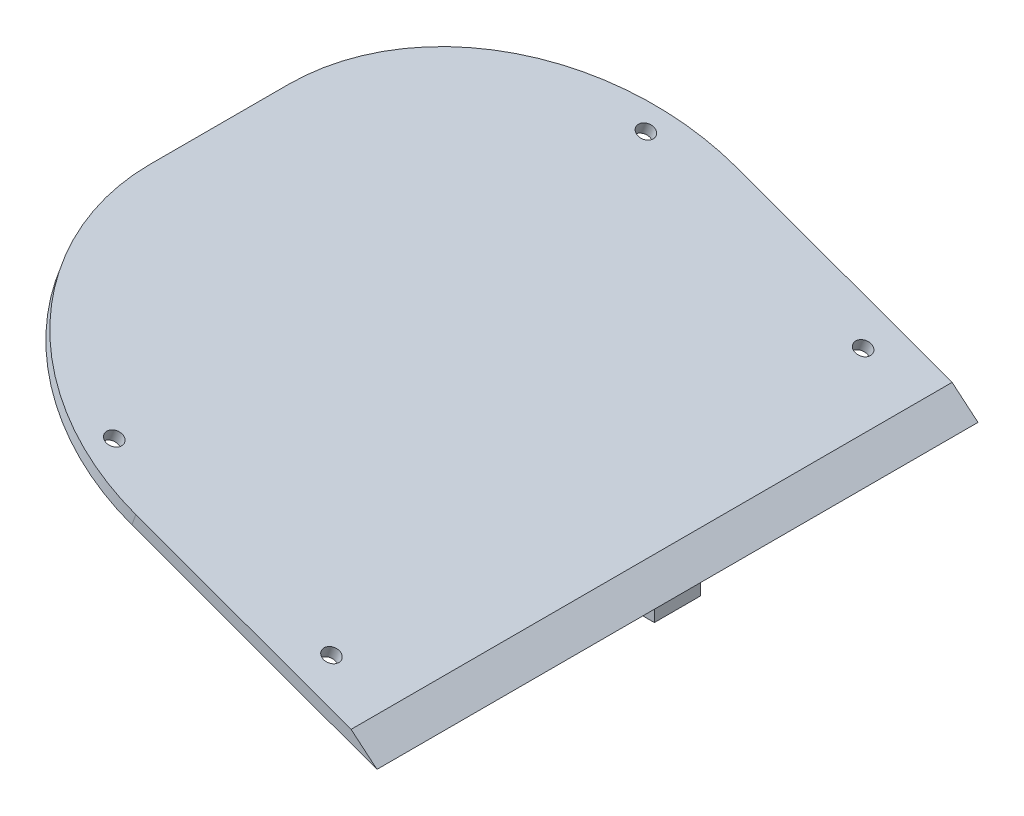
SolidWorks part; units mm, degrees
ref_plane "Piano frontale" through (0, 0, 0) normal (0, 0, 1) x (1, 0, 0)
ref_plane "Piano superiore" through (0, 0, 0) normal (0, 1, 0) x (1, 0, 0)
ref_plane "Piano destro" through (0, 0, 0) normal (1, 0, 0) x (0, 0, -1)
sketch "Schizzo1" plane through (0, 0, 0) normal (0, 0, 1) x (1, 0, 0)
  line L0 (0, 0) -> (-100, 0)
  line L1 (-100, 0) -> (-100, 38.897)
  line L3 (0, 0) -> (0, 2.5)
  line L4 (0, 2.5) -> (-100, 38.897)
  dimension "D1" = 2.5
  dimension "D2" = 100
  dimension "D3" = 20
extrude "Estrusione-Estrusione1" add sketch "Schizzo1" along normal blind 5 and the other way blind 5
sketch "Schizzo18" plane through (0, 0, 0) normal (0, -1, 0) x (1, 0, 0)
  line L0 (0, 0) -> (-80, 0) construction
  line L1 (-100, 5) -> (0, 5) construction
  line L2 (-87.5, 5) -> (-72.5, 5)
  arc A0 (-72.5, 5) -> (-87.5, 5) centre (-80, 5) ccw
  dimension "D2" = 15
  dimension "D1" = 80
extrude "Estrusione-Estrusione3" add sketch "Schizzo18" against normal blind 5
sketch "Schizzo19" plane through (0, 5, 0) normal (0, 1, 0) x (1, 0, 0)
  line L0 (-80, -12.5) -> (-80, -8.5) construction
  arc A0 (-87.5, -5) -> (-72.5, -5) centre (-80, -5) ccw construction
  dimension "D1" = 4
hole_wizard "Foro per Vite M3-1" positions "Schizzo3D1" profile "Schizzo20" hole size "M3" standard "ISO" end condition up to next
sketch3d "Schizzo3D1"
  point P0 (-80, 5, 8.5)
sketch "Schizzo20" plane through (-80, 5, 8.5) normal (1, 0, 0) x (0, 0, 1)
  line L0 (0, 0) -> (0, 5)
  line L1 (0, 5) -> (1.7, 5)
  line L2 (1.7, 5) -> (1.7, 0)
  line L5 (1.7, 0) -> (0, 0)
  line L11 (0, -6.35) -> (0, 107.95) construction
  dimension "Thru Hole Dia." = 3.4
  dimension "Thru Hole Depth" = 5
mirror "Specchia2" about plane through (0, 0, 0) normal (0, 0, 1) of "Foro per Vite M3-1", "Estrusione-Estrusione3"
sketch "Schizzo26" plane through (0.8035, 2.2076, 0) normal (0.342, 0.9397, 0) x (0.9397, -0.342, 0)
  line L0 (-0.8551, 5) -> (-0.8551, -5) construction
  line L1 (-0.8551, 65) -> (-107.2728, 65)
  line L2 (-0.8551, 65) -> (-0.8551, -65)
  line L3 (-0.8551, -65) -> (-107.2728, -65)
  line L4 (-107.2728, 65) -> (-107.2728, -65)
  line L5 (-107.2728, 5) -> (-107.2728, -5) construction
  point P8 (-0.8551, 0)
  dimension "D1" = 130
extrude "Estrusione-Estrusione5" add sketch "Schizzo26" along normal blind 2.5
sketch "Schizzo27" plane through (0, 0, 0) normal (0, -1, 0) x (1, 0, 0)
  line L0 (0, 0) -> (-45, 0) construction
  line L1 (-45, 0) -> (-45, 20.7814) construction
  dimension "D1" = 45
ref_plane "Piano4" through (-39.736, 14.4627, 0) normal (0.9397, -0.342, 0) x (0, 0, 1)
sketch "Schizzo29" plane through (-39.736, 14.4627, 0) normal (0.9397, -0.342, 0) x (0, 0, 1)
  line L0 (5, 10.3909) -> (65, -2.3492)
  line L2 (5, 24.7965) -> (5, 0) construction
  line L3 (0, 15.3909) -> (20.7814, 15.3909) construction
  dimension "D1" = 5
rib "Nervatura2" sketch "Schizzo29" sketch "Schizzo29" thickness 10 extrusion direction parallel to sketch draft on no parameters "D1"=10
mirror "Specchia3" about plane through (0, 0, 0) normal (0, 0, 1) of "Nervatura2"
chamfer "Smusso1" distance 2.5 angle 70 1 edges at (0.8551, 4.8492, 0) first distance on face at (0.285, 3.2831, 0)
fillet "Raccordo1" radius 50 2 edges at (-99.5725, 40.0716, -65) (-99.5725, 40.0716, 65)
sketch "Schizzo30" plane through (1.6585, 4.5568, 0) normal (0.342, 0.9397, 0) x (0.9397, -0.342, 0)
  line L0 (-7.7237, -65) -> (-7.7237, 65) construction
  line L1 (-20.2237, 57.5) -> (-70.2237, 57.5) construction
  line L2 (-20.2237, 57.5) -> (-20.2237, -57.5) construction
  line L3 (-20.2237, -57.5) -> (-70.2237, -57.5) construction
  line L4 (-70.2237, 57.5) -> (-70.2237, -57.5) construction
  line L5 (-20.2237, 57.5) -> (-70.2237, -57.5) construction
  line L6 (-20.2237, -57.5) -> (-70.2237, 57.5) construction
  point P0 (-45.2237, 0)
  dimension "D1" = 115
  dimension "D2" = 50
  dimension "D3" = 37.5
hole_wizard "Foro per Vite M3-2" positions "Schizzo31" profile "Schizzo32" hole size "M3" standard "ISO" end condition up to next
sketch "Schizzo31" plane through (1.6585, 4.5568, 0) normal (0.342, 0.9397, 0) x (0.9397, -0.342, 0)
  point P0 (-70.2237, 57.5)
  point P2 (-70.2237, -57.5)
  point P4 (-20.2237, -57.5)
  point P8 (-20.2237, 57.5)
sketch "Schizzo32" plane through (-64.3302, 28.5747, -57.5) normal (0, 0, 1) x (-0.9397, 0.342, 0)
  line L0 (0, 0) -> (0, 2.5)
  line L1 (0, 2.5) -> (1.7, 2.5)
  line L2 (1.7, 2.5) -> (1.7, 0)
  line L5 (1.7, 0) -> (0, 0)
  line L11 (0, -6.35) -> (0, 107.95) construction
  dimension "Thru Hole Dia." = 3.4
  dimension "Thru Hole Depth" = 2.5
